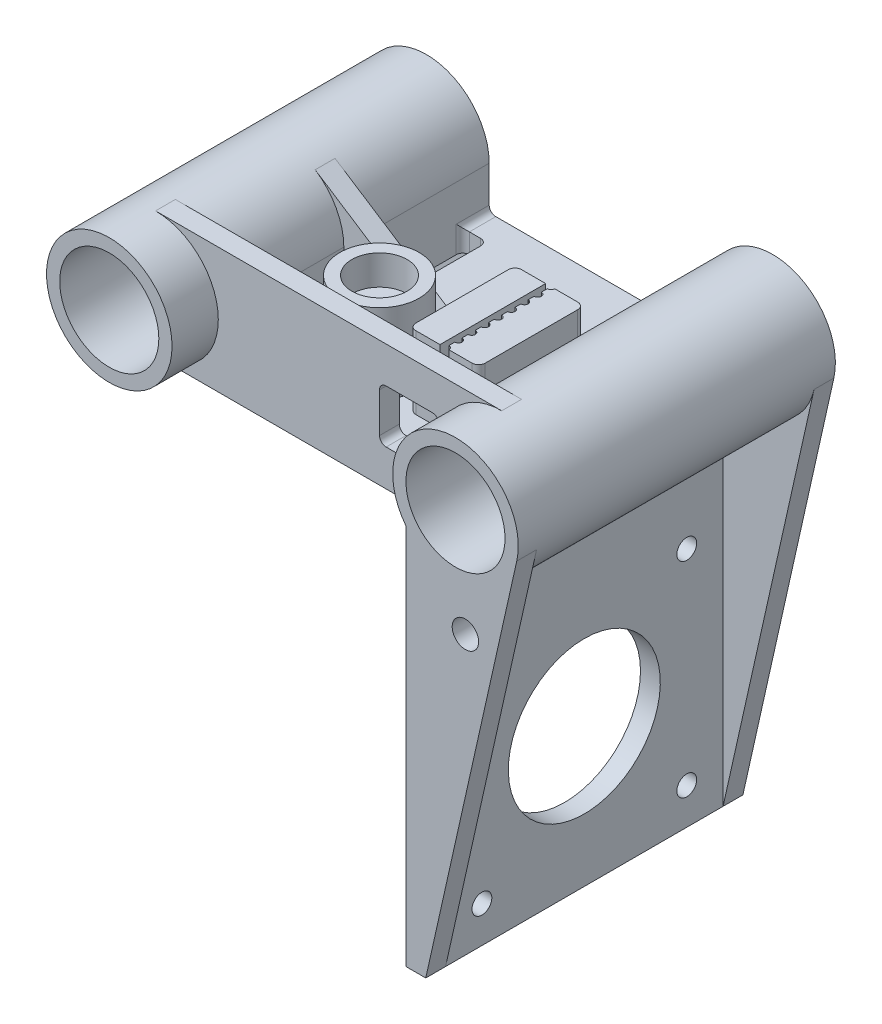
SolidWorks part; units mm, degrees
material "PC High Viscosity"
ref_plane "Front Plane" through (0, 0, 0) normal (0, 0, 1) x (1, 0, 0)
ref_plane "Top Plane" through (0, 0, 0) normal (0, 1, 0) x (1, 0, 0)
ref_plane "Right Plane" through (0, 0, 0) normal (1, 0, 0) x (0, 0, -1)
sketch "Sketch1" plane through (0, 0, 0) normal (0, 0, 1) x (1, 0, 0)
  circle A14 centre (0, 0) radius 7.5
  circle A15 centre (52.4, 0) radius 7.5
  circle A16 centre (0, 0) radius 9.5
  circle A17 centre (52.4, 0) radius 9.5
extrude "Boss-Extrude1" add sketch "Sketch1" along normal blind 48
sketch "Sketch2" plane through (0, 0, 0) normal (0, 0, -1) x (-1, 0, 0)
  line L0 (0, -9.5) -> (-52.4, -9.5)
  line L1 (-9.5, 0) -> (-9.5, -5.5)
  line L2 (-42.9, 0) -> (-42.9, -5.5)
  line L5 (-41.9, -6.5) -> (-10.5, -6.5)
  arc A0 (0, -9.5) -> (-9.5, 0) centre (0, 0) cw
  arc A4 (-42.9, 0) -> (-52.4, -9.5) centre (-52.4, 0) cw
  arc A5 (-42.9, -5.5) -> (-41.9, -6.5) centre (-41.9, -5.5) ccw
  arc A6 (-9.5, -5.5) -> (-10.5, -6.5) centre (-10.5, -5.5) cw
  dimension "D1" = 1
extrude "Boss-Extrude2" add sketch "Sketch2" against normal blind 38
sketch "Sketch3" plane through (0, 0, 38) normal (0, 0, 1) x (1, 0, 0)
  line L0 (52.4, -9.5) -> (0, -9.5) construction
  line L1 (0, 9.5) -> (52.4, 9.5)
  line L2 (52.4, -9.5) -> (0, -9.5)
  arc A0 (0, 9.5) -> (0, -9.5) centre (0, 0) cw
  circle A1 centre (0, 0) radius 9.5 construction
  arc A2 (0, -9.5) -> (9.5, 0) centre (0, 0) ccw construction
  arc A3 (52.4, 9.5) -> (52.4, -9.5) centre (52.4, 0) ccw
  circle A4 centre (52.4, 0) radius 9.5 construction
extrude "Boss-Extrude3" add sketch "Sketch3" along normal blind 3
sketch "Sketch4" plane through (0, 0, 0) normal (0, 0, -1) x (-1, 0, 0)
  line L0 (-4.5, -63.6) -> (9.2706, -2.075)
  line L8 (-47.9, -63.6) -> (-61.6706, -2.075)
  line L9 (-4.5, -63.6) -> (-47.9, -63.6)
  line L10 (0, -9.5) -> (-52.4, -9.5)
  arc A1 (0, -9.5) -> (9.2706, -2.075) centre (0, 0) ccw
  arc A2 (-52.4, -9.5) -> (-61.6706, -2.075) centre (-52.4, 0) cw
extrude "Boss-Extrude4" add sketch "Sketch4" against normal blind 3
sketch "Sketch5" plane through (0, -9.5, 0) normal (0, -1, 0) x (1, 0, 0)
  line L7 (13.2, 3) -> (16.2, 3)
  line L9 (16.2, 19) -> (16.2, 3)
  line L10 (13.2, 3) -> (13.2, 19)
  line L11 (13.2, 19) -> (16.2, 19)
extrude "Boss-Extrude5" add sketch "Sketch5" along normal blind 16
sketch "Sketch6" plane through (13.2, 0, 0) normal (-1, 0, 0) x (0, 0, 1)
  line L0 (3, -25.5) -> (19, -9.5)
  line L1 (19, -9.5) -> (19, -25.5)
  line L2 (19, -25.5) -> (3, -25.5)
extrude "Cut-Extrude1" cut sketch "Sketch6" against normal up to surface (3 mm away) up to face at (16.2, -17.5, 11)
sketch "Sketch7" plane through (0, 0, 48) normal (0, 0, 1) x (1, 0, 0)
  line L8 (61.6706, -2.075) -> (47.9, -63.6)
  line L10 (44.9, -5.831) -> (44.9, -63.6)
  line L11 (47.9, -63.6) -> (44.9, -63.6)
  arc A8 (61.6706, -2.075) -> (44.9, -5.831) centre (52.4, 0) cw
extrude "Boss-Extrude6" add sketch "Sketch7" against normal blind 3
sketch "Sketch10" plane through (0, 0, 41) normal (0, 0, 1) x (1, 0, 0)
  line L0 (44.9, -9.5) -> (52.4, -9.5)
  line L3 (44.9, -9.5) -> (44.9, -5.831)
  arc A0 (52.4, -9.5) -> (44.9, -5.831) centre (52.4, 0) cw
extrude "Boss-Extrude10" add sketch "Sketch10" along normal up to surface (4 mm away) up to face at (50.1404, -35.1058, 45)
sketch "Sketch11" plane through (0, -9.5, 0) normal (0, -1, 0) x (1, 0, 0)
  line L0 (44.9, 45) -> (47.9, 45)
  line L1 (47.9, 45) -> (47.9, 3)
  line L2 (47.9, 3) -> (44.9, 3)
  line L4 (44.9, 3) -> (44.9, 45)
extrude "Boss-Extrude11" add sketch "Sketch11" along normal up to surface (54.1 mm away) up to face at (46.4, -63.6, 46.5)
sketch "Sketch12" plane through (0, 0, 3) normal (0, 0, 1) x (1, 0, 0)
  line L1 (12.2, -10.5) -> (10.5, -10.5)
  line L3 (13.2, -11.5) -> (13.2, -23.5)
  line L6 (12.2, -24.5) -> (10.5, -24.5)
  line L8 (9.5, -11.5) -> (9.5, -23.5)
  line L10 (44.9, -42.55) -> (-0.2114, -42.55)
  line L12 (-0.2114, -42.55) -> (4.5, -63.6)
  line L13 (4.5, -63.6) -> (44.9, -63.6)
  line L14 (44.9, -63.6) -> (44.9, -42.55)
  circle A0 centre (24.3, -36.55) radius 1.5
  circle A1 centre (10.3, -36.55) radius 1.5
  arc A2 (10.5, -24.5) -> (9.5, -23.5) centre (10.5, -23.5) cw
  arc A3 (13.2, -23.5) -> (12.2, -24.5) centre (12.2, -23.5) cw
  arc A4 (12.2, -10.5) -> (13.2, -11.5) centre (12.2, -11.5) cw
  arc A5 (10.5, -10.5) -> (9.5, -11.5) centre (10.5, -11.5) ccw
extrude "Cut-Extrude2" cut sketch "Sketch12" against normal up to surface (3 mm away) up to face at (26.2, -13.4804, 0)
sketch "Sketch14" plane through (0, -9.5, 0) normal (0, -1, 0) x (1, 0, 0)
  circle A0 centre (21.4, 28.5) radius 4.125
extrude "Boss-Extrude12" add sketch "Sketch14" along normal blind 4
sketch "Sketch16" plane through (0, -6.5, 0) normal (0, 1, 0) x (1, 0, 0)
  circle A0 centre (21.4, -28.5) radius 6
extrude "Boss-Extrude13" add sketch "Sketch16" along normal blind 12
sketch "Sketch17" plane through (0, 5.5, 0) normal (0, 1, 0) x (1, 0, 0)
  circle A0 centre (21.4, -28.5) radius 4.175
extrude "Cut-Extrude4" cut sketch "Sketch17" against normal blind 4.5
sketch "Sketch18" plane through (0, 1, 0) normal (0, 1, 0) x (1, 0, 0)
  circle A0 centre (21.4, -28.5) radius 2
extrude "Cut-Extrude5" cut sketch "Sketch18" against normal up to surface (14.5 mm away) up to face at (25.525, -13.5, 28.5)
sketch "Sketch19" plane through (0, 0, 41) normal (0, 0, 1) x (1, 0, 0)
  line L4 (34.9, 4) -> (41.9, 4)
  line L5 (33.9, 3) -> (33.9, -3)
  line L6 (34.9, -4) -> (41.9, -4)
  line L7 (42.9, 3) -> (42.9, -3)
  arc A2 (41.9, -4) -> (42.9, -3) centre (41.9, -3) ccw
  arc A3 (41.9, 4) -> (42.9, 3) centre (41.9, 3) cw
  arc A4 (34.9, -4) -> (33.9, -3) centre (34.9, -3) cw
  arc A5 (33.9, 3) -> (34.9, 4) centre (34.9, 3) cw
extrude "Cut-Extrude6" cut sketch "Sketch19" against normal up to surface (3 mm away) up to face at (26.2, -0.1849, 38)
sketch "Sketch20" plane through (47.9, 0, 0) normal (1, 0, 0) x (0, 0, -1)
  circle A0 centre (-8.5, -58.1) radius 1.5
  circle A1 centre (-39.5, -58.1) radius 1.5
  circle A2 centre (-8.5, -27.1) radius 1.5
  circle A3 centre (-24, -42.6) radius 11.5
  circle A5 centre (-8.5, -15.55) radius 1.5
  point P2 (0, 0)
  point P3 (0, 0)
  point P4 (0, 0)
extrude "Cut-Extrude8" cut sketch "Sketch20" against normal up to surface (3 mm away) up to face at (44.9, -30.3702, 23)
sketch "Sketch21" plane through (0, -6.5, 0) normal (0, 1, 0) x (1, 0, 0)
  line L6 (30.4, -32) -> (38.9, -32)
  line L7 (29.4, -31) -> (29.4, -17)
  line L8 (30.4, -16) -> (38.9, -16)
  line L9 (39.9, -31) -> (39.9, -17)
  arc A0 (38.9, -16) -> (39.9, -17) centre (38.9, -17) cw
  arc A1 (30.4, -16) -> (29.4, -17) centre (30.4, -17) ccw
  arc A2 (38.9, -32) -> (39.9, -31) centre (38.9, -31) ccw
  arc A3 (29.4, -31) -> (30.4, -32) centre (30.4, -31) ccw
extrude "Boss-Extrude14" add sketch "Sketch21" along normal blind 11
sketch "Sketch22" plane through (0, 4.5, 0) normal (0, 1, 0) x (1, 0, 0)
  line L0 (34.845, -16.555) -> (34.845, -17.445)
  line L1 (34.845, -18.555) -> (34.845, -19.445)
  line L16 (34.845, -20.555) -> (34.845, -21.445)
  line L18 (34.845, -22.555) -> (34.845, -23.445)
  line L26 (34.05, -32) -> (34.05, -16)
  line L29 (34.05, -16) -> (35.4, -16)
  line L30 (34.05, -32) -> (35.4, -32)
  line L31 (34.845, -24.555) -> (34.845, -25.445)
  line L32 (34.845, -26.555) -> (34.845, -27.445)
  line L33 (34.845, -28.555) -> (34.845, -29.445)
  line L34 (34.845, -30.555) -> (34.845, -31.445)
  arc A10 (34.845, -18.555) -> (34.845, -17.445) centre (34.845, -18) ccw
  arc A11 (34.845, -16.555) -> (35.4, -16) centre (34.845, -16) ccw
  arc A12 (34.845, -20.555) -> (34.845, -19.445) centre (34.845, -20) ccw
  arc A13 (34.845, -21.445) -> (34.845, -22.555) centre (34.845, -22) cw
  arc A14 (34.845, -31.445) -> (35.4, -32) centre (34.845, -32) cw
  arc A18 (34.845, -23.445) -> (34.845, -24.555) centre (34.845, -24) cw
  arc A19 (34.845, -30.555) -> (34.845, -29.445) centre (34.845, -30) ccw
  arc A20 (34.845, -28.555) -> (34.845, -27.445) centre (34.845, -28) ccw
  arc A21 (34.845, -26.555) -> (34.845, -25.445) centre (34.845, -26) ccw
extrude "Cut-Extrude9" cut sketch "Sketch22" against normal blind 9
sketch "Sketch23" plane through (0, 0, 45) normal (0, 0, -1) x (-1, 0, 0)
  circle A0 centre (-53.9, -15.55) radius 2
extrude "Cut-Extrude10" cut sketch "Sketch23" against normal up to surface (3 mm away) up to face at (49.1023, -30.4707, 48)
sketch "Sketch24" plane through (0, -9.5, 0) normal (0, -1, 0) x (1, 0, 0)
  line L8 (10.5, 4) -> (12.2, 4)
  line L9 (9.5, 5) -> (9.5, 17)
  line L10 (10.5, 18) -> (12.2, 18)
  line L11 (13.2, 5) -> (13.2, 17)
  line L13 (10.5, 37) -> (12.2, 37)
  line L14 (9.5, 36) -> (9.5, 24)
  line L15 (10.5, 23) -> (12.2, 23)
  line L16 (13.2, 36) -> (13.2, 24)
  arc A0 (12.2, 37) -> (13.2, 36) centre (12.2, 36) cw
  arc A1 (9.5, 36) -> (10.5, 37) centre (10.5, 36) cw
  arc A2 (12.2, 23) -> (13.2, 24) centre (12.2, 24) ccw
  arc A3 (9.5, 24) -> (10.5, 23) centre (10.5, 24) ccw
  arc A4 (12.2, 4) -> (13.2, 5) centre (12.2, 5) ccw
  arc A5 (12.2, 18) -> (13.2, 17) centre (12.2, 17) cw
  arc A6 (10.5, 18) -> (9.5, 17) centre (10.5, 17) ccw
  arc A7 (10.5, 4) -> (9.5, 5) centre (10.5, 5) cw
extrude "Cut-Extrude11" cut sketch "Sketch24" against normal up to vertex (4 mm away) up to point (9.5, -5.5, 0)
sketch "Sketch25" plane through (0, -6.5, 0) normal (0, 1, 0) x (1, 0, 0)
  line L3 (9.5, -22) -> (27.5, -22)
  line L4 (9.5, -22) -> (9.5, -19)
  line L5 (9.5, -19) -> (27.5, -19)
  line L6 (27.5, -22) -> (27.5, -19)
extrude "Boss-Extrude15" add sketch "Sketch25" along normal up to surface (16 mm away) up to face at (26.2, 9.5, 39.5)
sketch "Sketch26" plane through (0, 0, 19) normal (0, 0, -1) x (-1, 0, 0)
  line L0 (0, 9.5) -> (-9.5, 9.5)
  line L1 (-9.5, 9.5) -> (-9.5, 0)
  arc A0 (-9.5, 0) -> (0, 9.5) centre (0, 0) cw
extrude "Boss-Extrude16" add sketch "Sketch26" against normal up to surface (3 mm away) up to face at (15.6321, 0.0488, 22)
sketch "Sketch27" plane through (0, 0, 19) normal (0, 0, -1) x (-1, 0, 0)
  line L0 (-27.5, -6.5) -> (-27.5, 9.5)
  line L1 (-27.5, -6.5) -> (-5.1662, 7.9725)
  line L2 (0, 9.5) -> (-27.5, 9.5)
  arc A1 (-5.1662, 7.9725) -> (0, 9.5) centre (0, 0) cw
extrude "Cut-Extrude12" cut sketch "Sketch27" against normal up to surface (3 mm away) up to face at (14.3767, 0.3767, 22)
sketch "Sketch28" plane through (0, 0, 45) normal (0, 0, -1) x (-1, 0, 0)
  line L1 (-47.9, -9.5) -> (-50.9, -9.5)
  line L2 (-47.9, -9.5) -> (-47.9, -21.5)
  line L3 (-47.9, -21.5) -> (-50.9, -21.5)
  line L4 (-50.9, -9.5) -> (-50.9, -21.5)
  line L7 (-48.85, -10) -> (-49.95, -10)
  line L8 (-48.85, -10) -> (-48.85, -21)
  line L9 (-48.85, -21) -> (-49.95, -21)
  line L10 (-49.95, -10) -> (-49.95, -21)
extrude "Boss-Extrude17" add sketch "Sketch28" along normal blind 1
